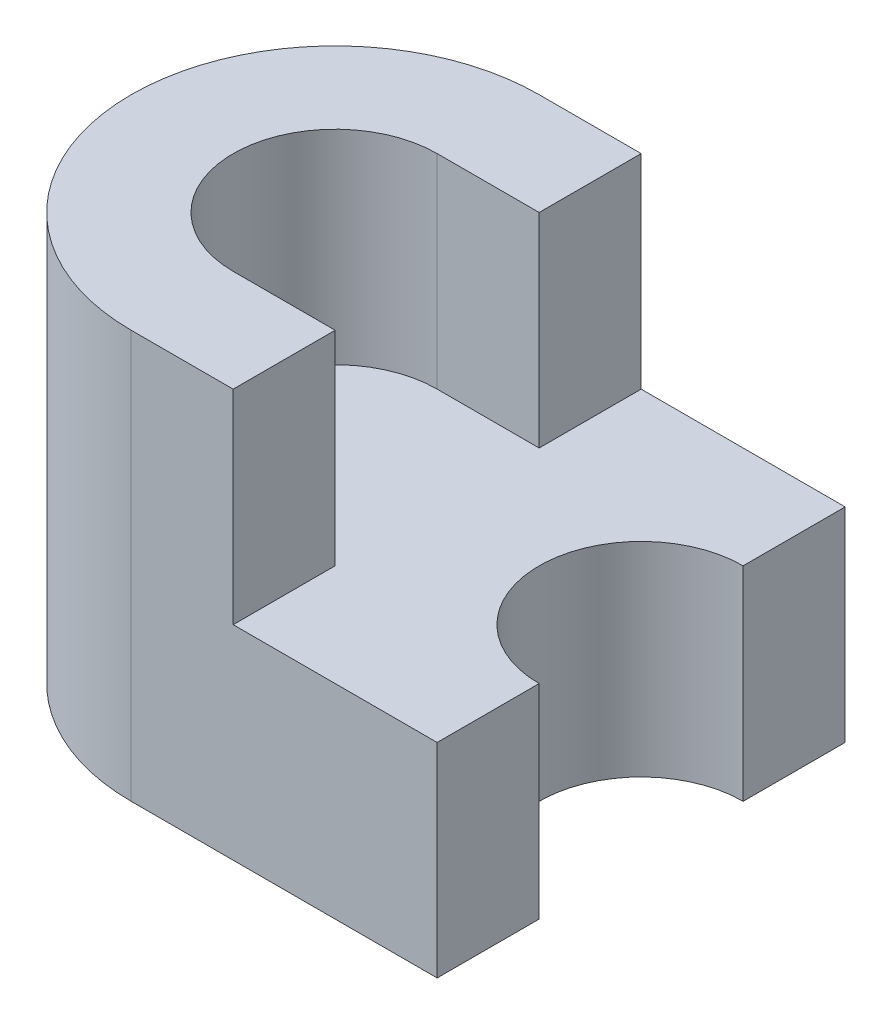
SolidWorks part; units mm, degrees
material "Cast Alloy Steel"
ref_plane "Front Plane" through (0, 0, 0) normal (0, 0, 1) x (1, 0, 0)
ref_plane "Top Plane" through (0, 0, 0) normal (0, 1, 0) x (1, 0, 0)
ref_plane "Right Plane" through (0, 0, 0) normal (1, 0, 0) x (0, 0, -1)
sketch "Sketch1" plane through (0, 0, 0) normal (0, 1, 0) x (1, 0, 0)
  line L5 (0, 0) -> (50, 0)
  line L6 (0, 0) -> (0, 40)
  line L7 (0, 40) -> (50, 40)
  line L8 (50, 0) -> (50, 40)
  dimension "D1" = 40
  dimension "D2" = 50
sketch "Sketch5" plane through (0, 0, 0) normal (0, 1, 0) x (1, 0, 0)
extrude "Boss-Extrude2" add sketch "Sketch1" along normal blind 40
sketch "circle" plane through (0, 0, 0) normal (0, -1, 0) x (-1, 0, 0)
  line L1 (-50, 10) -> (-50, 30)
  arc A1 (-50, 30) -> (-50, 10) centre (-50, 20) cw
sketch "Sketch9" plane through (0, 0, 0) normal (0, -1, 0) x (1, 0, 0)
  line L3 (10.0652, -79.7818) -> (10.0652, -80.2855)
extrude "Cut-Extrude1" cut sketch "circle" against normal through all
sketch "Sketch10" plane through (0, 40, 0) normal (0, 1, 0) x (1, 0, 0)
  line L1 (50, 40) -> (30.0023, 40)
  line L2 (50, 40) -> (50, 0)
  line L3 (50, 0) -> (30.0023, 0)
  line L4 (30.0023, 40) -> (30.0023, 0)
extrude "Cut-Extrude2" cut sketch "Sketch10" against normal blind 20
sketch "Sketch11" plane through (0, 40, 0) normal (0, 1, 0) x (1, 0, 0)
  line L0 (30.0023, 40) -> (0, 40) construction
  line L1 (30.0023, 40) -> (20.0023, 40)
  line L2 (30.0023, 40) -> (30.0023, 30)
  line L3 (30.0023, 30) -> (20.0023, 30)
  line L4 (20.0023, 40) -> (20.0023, 30)
  line L5 (30.0023, 40) -> (30.0023, 0) construction
  line L6 (20.0023, 30) -> (20.0023, 10)
  line L7 (30.0023, 0) -> (20.0023, 0)
  line L8 (30.0023, 0) -> (30.0023, 10)
  line L9 (30.0023, 10) -> (20.0023, 10)
  line L10 (20.0023, 0) -> (20.0023, 10)
  dimension "D1" = 10
  dimension "D2" = 10
  dimension "D3" = 10
  dimension "D4" = 10
sketch "Sketch12" plane through (0, 40, 0) normal (0, 1, 0) x (1, 0, 0)
  line L1 (20.0023, 30) -> (30.0023, 30)
  line L2 (20.0023, 30) -> (20.0023, 10)
  line L3 (20.0023, 10) -> (30.0023, 10)
  line L4 (30.0023, 30) -> (30.0023, 10)
  point P6 (0, 0)
  point P11 (0, 0)
extrude "Cut-Extrude3" cut sketch "Sketch12" against normal blind 20
sketch "Sketch14" plane through (0, 40, 0) normal (0, 1, 0) x (1, 0, 0)
  arc A0 (20.0023, 10) -> (20.0023, 30) centre (20.0023, 20) cw
extrude "Cut-Extrude6" cut sketch "Sketch14" against normal blind 20 and the other way through all flip side to cut
fillet "Fillet3" radius 20 2 edges at (0, 20, -40) (0, 20, 0)
